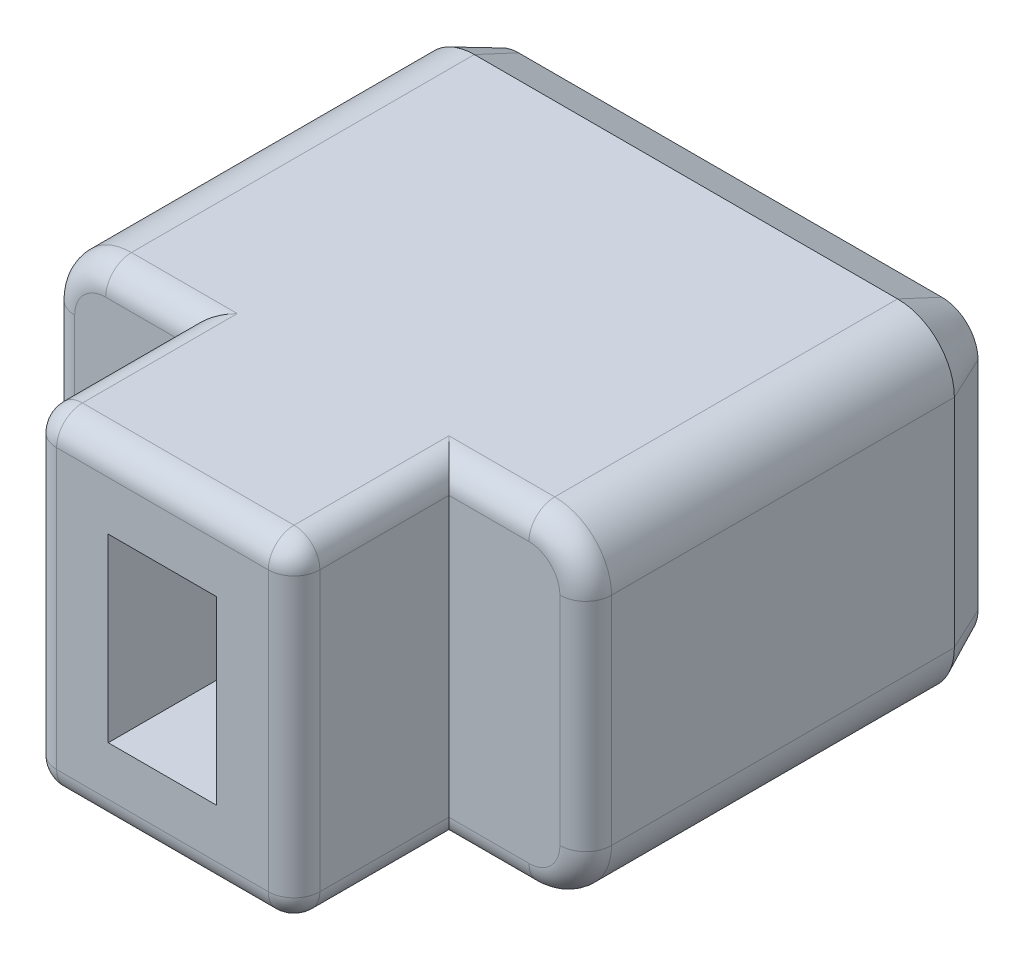
SolidWorks part; units mm, degrees
ref_plane "Plan de face" through (0, 0, 0) normal (0, 0, 1) x (1, 0, 0)
ref_plane "Plan de dessus" through (0, 0, 0) normal (0, 1, 0) x (1, 0, 0)
ref_plane "Plan de droite" through (0, 0, 0) normal (1, 0, 0) x (0, 0, -1)
sketch "Esquisse2" plane through (0, 0, 0) normal (0, 0, 1) x (1, 0, 0)
  line L1 (1.1, 0) -> (9.3, 0)
  line L2 (0, 1.1) -> (0, 5.3)
  line L3 (1.1, 6.4) -> (9.3, 6.4)
  line L4 (10.4, 1.1) -> (10.4, 5.3)
  arc A0 (9.3, 6.4) -> (10.4, 5.3) centre (9.3, 5.3) cw
  arc A1 (9.3, 0) -> (10.4, 1.1) centre (9.3, 1.1) ccw
  arc A2 (1.1, 0) -> (0, 1.1) centre (1.1, 1.1) cw
  arc A3 (0, 5.3) -> (1.1, 6.4) centre (1.1, 5.3) cw
  point P7 (10.4, 6.4)
  point P12 (0, 0)
  point P15 (0, 6.4)
  dimension "D3" = 1.1
  dimension "D1" = 10.4
  dimension "D2" = 6.4
extrude "Boss.-Extru.1" add sketch "Esquisse2" along normal blind 11
sketch "Esquisse3" plane through (0, 0, 11) normal (0, 0, 1) x (1, 0, 0)
  line L0 (0, 5.3) -> (0, 1.1) construction
  line L1 (4.15, 4.95) -> (6.25, 4.95)
  line L2 (4.15, 4.95) -> (4.15, 1.45)
  line L3 (4.15, 1.45) -> (6.25, 1.45)
  line L4 (6.25, 4.95) -> (6.25, 1.45)
  line L5 (10.4, 1.1) -> (10.4, 5.3) construction
  line L6 (9.3, 6.4) -> (1.1, 6.4) construction
  line L7 (1.1, 0) -> (9.3, 0) construction
  dimension "D1" = 2.1
  dimension "D2" = 3.5
  dimension "D3" = 4.15
  dimension "D4" = 4.15
  dimension "D5" = 1.45
  dimension "D6" = 1.45
extrude "Enlèv. mat.-Extru.1" cut sketch "Esquisse3" against normal blind 3
sketch "Esquisse4" plane through (0, 0, 11) normal (0, 0, 1) x (1, 0, 0)
  line L0 (2.65, 6.4) -> (2.65, 0)
  line L1 (9.3, 6.4) -> (1.1, 6.4) construction
  line L2 (1.1, 0) -> (9.3, 0) construction
  line L3 (2.65, 0) -> (7.75, 0)
  line L4 (7.75, 0) -> (7.75, 6.4)
  line L5 (7.75, 6.4) -> (2.65, 6.4)
  line L6 (4.15, 4.95) -> (4.15, 1.45) construction
  line L7 (6.25, 1.45) -> (6.25, 4.95) construction
  dimension "D1" = 1.5
  dimension "D2" = 1.5
extrude "Enlèv. mat.-Extru.2" cut sketch "Esquisse4" against normal blind 3 flip side to cut
fillet "Congé1" radius 0.5 18 edges at (8.525, 0, 8) (10.0778, 0.3222, 8) (10.4, 3.2, 8) (10.0778, 6.0778, 8) (1.875, 6.4, 8) (0.3222, 6.0778, 8) (1.875, 0, 8) (0.3222, 0.3222, 8) (7.75, 6.4, 9.5) (2.65, 6.4, 9.5) (7.75, 0, 9.5) (2.65, 0, 9.5) (2.65, 3.2, 11) (5.2, 6.4, 11) (7.75, 3.2, 11) (5.2, 0, 11) (8.525, 6.4, 8) (0, 3.2, 8)
chamfer "Chanfrein1" distance 0.4 angle 65 8 edges at (5.2, 0, 0) (10.0778, 0.3222, 0) (0.3222, 0.3222, 0) (10.4, 3.2, 0) (0, 3.2, 0) (10.0778, 6.0778, 0) (0.3222, 6.0778, 0) (5.2, 6.4, 0) first distance on face at (5.2, 3.2, 0)
sketch "Esquisse5" plane through (0, 0, 0) normal (0, 0, -1) x (-1, 0, 0)
  line L0 (-0.4, 5.3) -> (-10, 5.3) construction
  arc A0 (-9.3, 6) -> (-10, 5.3) centre (-9.3, 5.3) ccw construction
  text T0 "3" font "Century Gothic" height 4
extrude "Enlèv. mat.-Extru.3" cut sketch "Esquisse5" against normal blind 0.3
extrude "Boss.-Extru.2" add sketch "Esquisse5<2>" along normal blind 0.3 separate body
sketch "Esquisse5<2>" plane through (0, 0, 0) normal (0, 0, -1) x (-1, 0, 0) same geometry as "Esquisse5"
